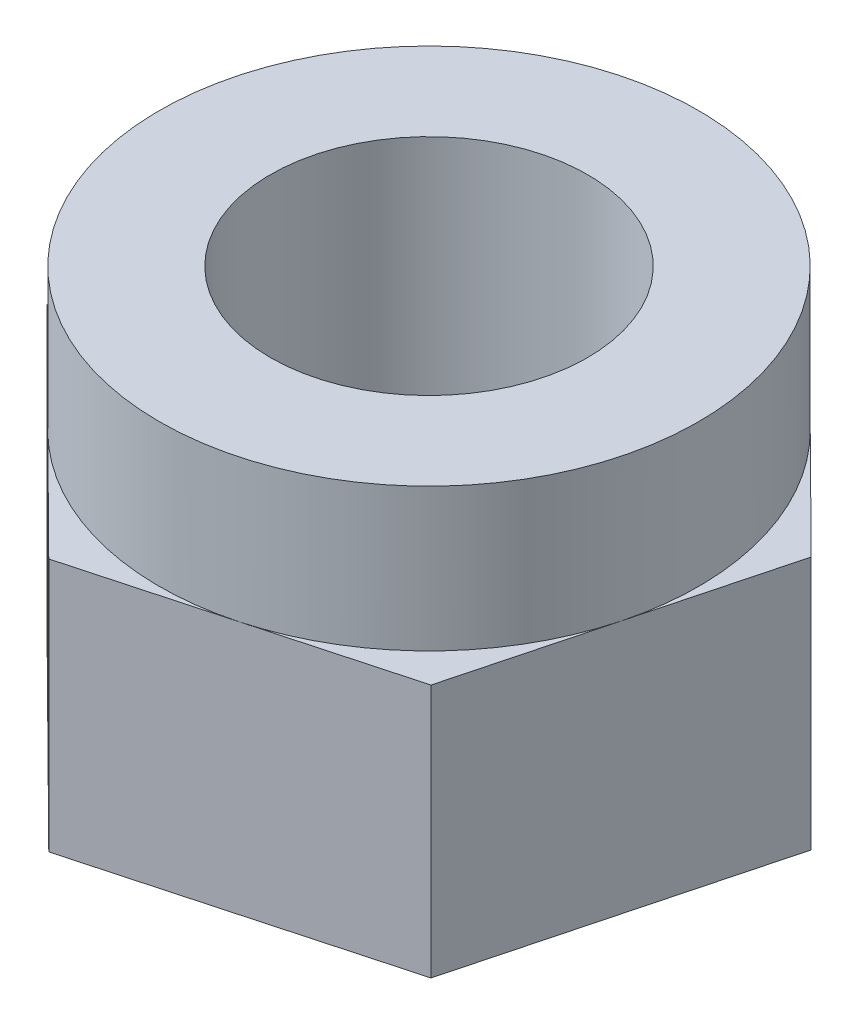
SolidWorks part; units mm, degrees
ref_plane "前视基准面" through (0, 0, 0) normal (0, 0, 1) x (1, 0, 0)
ref_plane "上视基准面" through (0, 0, 0) normal (0, 1, 0) x (1, 0, 0)
ref_plane "右视基准面" through (0, 0, 0) normal (1, 0, 0) x (0, 0, -1)
sketch "草图1" plane through (0, 0, 0) normal (0, 1, 0) x (1, 0, 0)
  line L1 (3.7876, 1.0332) -> (0.999, 3.7968)
  line L2 (0.999, 3.7968) -> (-2.7886, 2.7635)
  line L3 (-2.7886, 2.7635) -> (-3.7876, -1.0332)
  line L4 (-3.7876, -1.0332) -> (-0.999, -3.7968)
  line L5 (-0.999, -3.7968) -> (2.7886, -2.7635)
  line L6 (2.7886, -2.7635) -> (3.7876, 1.0332)
  circle A0 centre (0, 0) radius 3.4
  circle A1 centre (0, 0) radius 3.4 construction
  dimension "D1" = 6.8
extrude "凸台-拉伸1" add sketch "草图1" along normal blind 3.2 contours A0 L5 L6 | A0 L6 L1 | A0 L1 L2 | A0 L2 L3 | A0 L3 L4 | A0 | A0 L4 L5 region at (3.3902, 0, -0.9248) region at (0.8942, 0, -3.3984) region at (0, 0, 0) region at (2.496, 0, 2.4736) region at (-2.496, 0, -2.4736) region at (-0.8942, 0, 3.3984) region at (-3.3902, 0, 0.9248)
extrude "凸台-拉伸2" add sketch "草图1<3>" along normal blind 5 contours A0 region at (0, 0, 0)
sketch "草图1<3>" plane through (0, 0, 0) normal (0, 1, 0) x (1, 0, 0) same geometry as "草图1"
sketch "草图2" plane through (0, 0, 0) normal (0, 1, 0) x (1, 0, 0)
  circle A0 centre (0, 0) radius 2
  dimension "D1" = 4
extrude "切除-拉伸1" cut sketch "草图2" along normal blind 5
